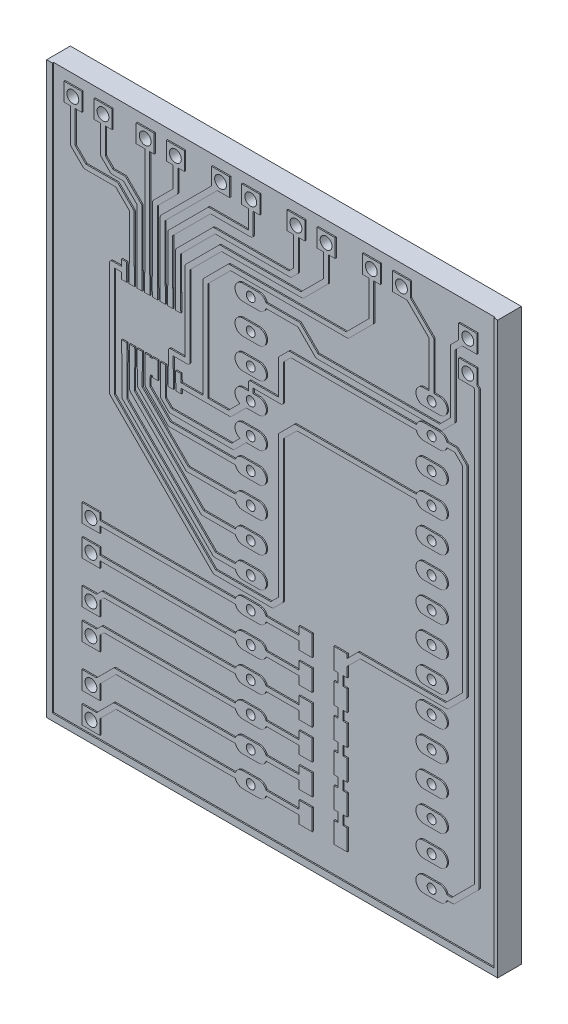
SolidWorks part; units mm, degrees
ref_plane "Front Plane" through (0, 0, 0) normal (0, 0, 1) x (1, 0, 0)
ref_plane "Top Plane" through (0, 0, 0) normal (0, 1, 0) x (1, 0, 0)
ref_plane "Right Plane" through (0, 0, 0) normal (1, 0, 0) x (0, 0, -1)
sketch "Model" plane through (0, 0, 0) normal (0, 0, 1) x (1, 0, 0)
  line L0 (2.413, 45.6438) -> (2.9718, 45.6438)
  line L1 (2.0066, 45.6438) -> (2.0066, 42.8498)
  line L2 (6.7831, 29.2576) -> (6.7754, 30.7326)
  line L3 (6.7754, 30.7326) -> (6.3254, 30.7302)
  line L4 (6.3254, 30.7302) -> (6.3331, 29.2553)
  line L5 (6.3331, 29.2553) -> (6.351, 29.2553)
  line L6 (7.4331, 29.261) -> (7.4253, 30.736)
  line L7 (7.4253, 30.736) -> (6.9753, 30.7336)
  line L8 (6.9753, 30.7336) -> (6.9831, 29.2587)
  line L9 (6.9831, 29.2587) -> (7.001, 29.2587)
  line L10 (8.0831, 29.2644) -> (8.0753, 30.7394)
  line L11 (8.0753, 30.7394) -> (7.6253, 30.737)
  line L12 (7.6253, 30.737) -> (7.633, 29.2621)
  line L13 (7.633, 29.2621) -> (7.651, 29.2622)
  line L14 (8.7331, 29.2678) -> (8.7324, 29.3986)
  line L15 (8.7253, 30.7428) -> (8.2753, 30.7404)
  line L16 (8.2753, 30.7404) -> (8.2831, 29.2655)
  line L18 (9.383, 29.2712) -> (9.3753, 30.7462)
  line L19 (9.3753, 30.7462) -> (8.9253, 30.7438)
  line L20 (8.9253, 30.7438) -> (8.9258, 30.6521)
  line L21 (8.933, 29.2689) -> (9.383, 29.2712)
  line L22 (10.033, 29.2746) -> (10.0253, 30.7496)
  line L23 (10.0253, 30.7496) -> (9.5753, 30.7473)
  line L24 (9.5753, 30.7473) -> (9.583, 29.2723)
  line L25 (9.583, 29.2723) -> (9.601, 29.2724)
  line L26 (10.683, 29.278) -> (10.6753, 30.753)
  line L27 (10.6753, 30.753) -> (10.6574, 30.7529)
  line L28 (10.2253, 30.7507) -> (10.233, 29.2757)
  line L29 (10.233, 29.2757) -> (10.683, 29.278)
  line L30 (11.333, 29.2814) -> (11.3309, 29.6926)
  line L31 (11.3253, 30.7564) -> (10.8753, 30.7541)
  line L32 (10.8753, 30.7541) -> (10.883, 29.2791)
  line L33 (10.883, 29.2791) -> (11.333, 29.2814)
  line L34 (11.3022, 35.1574) -> (11.2945, 36.6323)
  line L35 (11.2945, 36.6323) -> (11.2766, 36.6323)
  line L36 (10.8445, 36.63) -> (10.8522, 35.155)
  line L37 (10.8522, 35.155) -> (11.3022, 35.1574)
  line L38 (10.6523, 35.154) -> (10.6445, 36.6289)
  line L39 (10.6445, 36.6289) -> (10.6266, 36.6289)
  line L40 (10.1945, 36.6266) -> (10.2023, 35.1516)
  line L41 (10.2023, 35.1516) -> (10.6523, 35.154)
  line L42 (10.0023, 35.1506) -> (9.9946, 36.6255)
  line L43 (9.9946, 36.6255) -> (9.9766, 36.6254)
  line L44 (9.5445, 36.6232) -> (9.5523, 35.1482)
  line L45 (9.5523, 35.1482) -> (10.0023, 35.1506)
  line L46 (9.3523, 35.1472) -> (9.3445, 36.6221)
  line L47 (9.3445, 36.6221) -> (9.3266, 36.622)
  line L48 (8.8945, 36.6198) -> (8.9023, 35.1448)
  line L49 (8.9023, 35.1448) -> (9.3523, 35.1472)
  line L50 (8.7023, 35.1438) -> (8.6946, 36.6187)
  line L51 (8.6946, 36.6187) -> (8.6766, 36.6186)
  line L52 (8.2446, 36.6164) -> (8.2523, 35.1414)
  line L53 (8.2523, 35.1414) -> (8.7023, 35.1438)
  line L54 (8.0523, 35.1403) -> (8.0446, 36.6153)
  line L55 (8.0446, 36.6153) -> (8.0266, 36.6152)
  line L56 (7.5946, 36.613) -> (7.6023, 35.138)
  line L57 (7.6023, 35.138) -> (8.0523, 35.1403)
  line L58 (7.4023, 35.1369) -> (7.3946, 36.6119)
  line L59 (7.3946, 36.6119) -> (7.3766, 36.6118)
  line L60 (6.9446, 36.6096) -> (6.9523, 35.1346)
  line L61 (6.9523, 35.1346) -> (7.4023, 35.1369)
  line L62 (6.7523, 35.1335) -> (6.7446, 36.6085)
  line L63 (6.7446, 36.6085) -> (6.2946, 36.6062)
  line L64 (6.2946, 36.6062) -> (6.2974, 36.0731)
  line L65 (6.3023, 35.1312) -> (6.7523, 35.1335)
  line L66 (2.9718, 14.6558) -> (2.9718, 13.1318)
  line L67 (2.9718, 13.1318) -> (4.4958, 13.1318)
  line L68 (4.4958, 13.1318) -> (4.4958, 13.6906)
  line L69 (4.4958, 14.6558) -> (2.9718, 14.6558)
  line L70 (16.5354, 39.2938) -> (17.8562, 39.2938) construction
  line L71 (4.5466, 45.6438) -> (4.5466, 43.3578)
  line L72 (4.953, 45.6438) -> (5.5118, 45.6438)
  line L73 (16.5354, 39.9573) -> (17.8562, 39.9573)
  line L74 (2.9718, 17.1958) -> (2.9718, 15.6718)
  line L75 (2.9718, 15.6718) -> (4.4958, 15.6718)
  line L76 (4.4958, 15.6718) -> (4.4958, 16.2306)
  line L77 (4.4958, 17.1958) -> (2.9718, 17.1958)
  line L78 (8.2702, 45.6438) -> (8.2702, 36.6165)
  line L79 (8.6766, 45.6438) -> (9.0678, 45.6438)
  line L80 (16.5354, 38.6303) -> (17.8562, 38.6303)
  line L81 (10.6426, 45.6438) -> (10.6426, 43.8944)
  line L82 (2.9718, 8.5598) -> (2.9718, 7.0358)
  line L83 (2.9718, 7.0358) -> (4.4958, 7.0358)
  line L84 (4.4958, 7.0358) -> (4.4958, 8.2724)
  line L85 (4.2084, 8.5598) -> (2.9718, 8.5598)
  line L86 (11.049, 45.6438) -> (11.6078, 45.6438)
  line L87 (17.1958, 39.2938) -> (17.1958, 36.7538) construction
  line L88 (13.8938, 45.7336) -> (9.6297, 41.4695)
  line L89 (31.7754, 39.2938) -> (33.0962, 39.2938) construction
  line L90 (2.9718, 11.0998) -> (2.9718, 9.5758)
  line L91 (2.9718, 9.5758) -> (4.4958, 9.5758)
  line L92 (4.4958, 9.5758) -> (4.4958, 10.8124)
  line L93 (4.2084, 11.0998) -> (2.9718, 11.0998)
  line L94 (17.399, 45.6438) -> (17.9578, 45.6438)
  line L95 (20.8026, 45.6438) -> (20.8026, 43.188)
  line L96 (21.209, 45.6438) -> (21.7678, 45.6438)
  line L97 (18.4879, 39.0906) -> (21.1756, 39.0906)
  line L98 (2.9718, 2.4638) -> (2.9718, 0.9398)
  line L99 (2.9718, 0.9398) -> (4.4958, 0.9398)
  line L100 (4.4958, 0.9398) -> (4.4958, 2.1764)
  line L101 (4.2084, 2.4638) -> (2.9718, 2.4638)
  line L102 (23.3426, 45.6438) -> (23.3426, 43.696)
  line L103 (23.749, 45.6438) -> (24.3078, 45.6438)
  line L104 (31.7754, 39.9573) -> (33.0962, 39.9573)
  line L105 (27.1526, 45.6438) -> (27.1526, 42.68)
  line L106 (2.9718, 5.0038) -> (2.9718, 3.4798)
  line L107 (2.9718, 3.4798) -> (4.4958, 3.4798)
  line L108 (4.4958, 3.4798) -> (4.4958, 4.7164)
  line L109 (4.2084, 5.0038) -> (2.9718, 5.0038)
  line L110 (27.559, 45.6438) -> (28.1178, 45.6438)
  line L111 (31.7754, 38.6303) -> (33.0962, 38.6303)
  line L112 (31.7754, 36.7538) -> (33.0962, 36.7538) construction
  line L113 (30.3704, 45.6438) -> (32.2326, 43.7816)
  line L114 (3.9878, 45.6438) -> (4.5466, 45.6438)
  line L115 (5.5118, 45.6438) -> (5.5118, 47.1678)
  line L116 (5.5118, 47.1678) -> (3.9878, 47.1678)
  line L117 (3.9878, 47.1678) -> (3.9878, 45.6438)
  line L118 (34.7218, 44.9152) -> (34.0701, 44.2635)
  line L119 (31.7754, 37.4173) -> (33.0962, 37.4173)
  line L120 (31.7754, 36.0903) -> (33.0962, 36.0903)
  line L121 (4.4958, 2.1764) -> (5.85, 3.5306)
  line L122 (1.4478, 45.6438) -> (2.0066, 45.6438)
  line L123 (2.9718, 45.6438) -> (2.9718, 47.1678)
  line L124 (2.9718, 47.1678) -> (1.4478, 47.1678)
  line L125 (1.4478, 47.1678) -> (1.4478, 45.6438)
  line L126 (31.7754, 34.2138) -> (33.0962, 34.2138) construction
  line L127 (4.4958, 4.7164) -> (5.85, 6.0706)
  line L128 (31.7754, 34.8773) -> (33.0962, 34.8773)
  line L129 (4.4958, 8.2724) -> (4.834, 8.6106)
  line L130 (10.0838, 45.6438) -> (10.6426, 45.6438)
  line L131 (11.6078, 45.6438) -> (11.6078, 47.1678)
  line L132 (11.6078, 47.1678) -> (10.0838, 47.1678)
  line L133 (10.0838, 47.1678) -> (10.0838, 45.6438)
  line L134 (31.7754, 33.5503) -> (33.0962, 33.5503)
  line L135 (4.4958, 10.8124) -> (4.834, 11.1506)
  line L136 (31.7754, 31.6738) -> (33.0962, 31.6738) construction
  line L137 (4.4958, 13.6906) -> (7.2898, 13.6906)
  line L138 (7.5438, 45.6438) -> (8.2702, 45.6438)
  line L139 (9.0678, 45.6438) -> (9.0678, 47.1678)
  line L140 (9.0678, 47.1678) -> (7.5438, 47.1678)
  line L141 (7.5438, 47.1678) -> (7.5438, 45.6438)
  line L142 (4.4958, 14.097) -> (4.4958, 14.6558)
  line L143 (31.7754, 32.3373) -> (33.0962, 32.3373)
  line L144 (4.4958, 16.2306) -> (7.2898, 16.2306)
  line L145 (4.4958, 16.637) -> (4.4958, 17.1958)
  line L146 (16.4338, 45.6438) -> (16.9926, 45.6438)
  line L147 (17.9578, 45.6438) -> (17.9578, 47.1678)
  line L148 (17.9578, 47.1678) -> (16.4338, 47.1678)
  line L149 (16.4338, 47.1678) -> (16.4338, 45.6438)
  line L150 (31.7754, 31.0103) -> (33.0962, 31.0103)
  line L151 (6.9702, 36.6097) -> (6.9446, 36.6096)
  line L152 (7.6202, 36.6131) -> (7.5946, 36.613)
  line L153 (8.2702, 36.6165) -> (8.2446, 36.6164)
  line L154 (14.3788, 45.6438) -> (15.4178, 45.6438)
  line L155 (15.4178, 45.6438) -> (15.4178, 47.1678)
  line L156 (15.4178, 47.1678) -> (13.8938, 47.1678)
  line L157 (13.8938, 47.1678) -> (13.8938, 45.7336)
  line L158 (8.9202, 36.6199) -> (8.8945, 36.6198)
  line L159 (9.5702, 36.6233) -> (9.5445, 36.6232)
  line L160 (10.2202, 36.6267) -> (10.1945, 36.6266)
  line L161 (10.8702, 36.6301) -> (10.8445, 36.63)
  line L162 (29.1338, 45.6438) -> (30.3704, 45.6438)
  line L163 (30.6578, 45.9312) -> (30.6578, 47.1678)
  line L164 (30.6578, 47.1678) -> (29.1338, 47.1678)
  line L165 (29.1338, 47.1678) -> (29.1338, 45.6438)
  line L166 (6.7574, 29.2575) -> (6.7831, 29.2576)
  line L167 (7.4074, 29.2609) -> (7.4331, 29.261)
  line L168 (8.0574, 29.2643) -> (8.0831, 29.2644)
  line L170 (26.5938, 45.6438) -> (27.1526, 45.6438)
  line L171 (28.1178, 45.6438) -> (28.1178, 47.1678)
  line L172 (28.1178, 47.1678) -> (26.5938, 47.1678)
  line L173 (26.5938, 47.1678) -> (26.5938, 45.6438)
  line L174 (10.0074, 29.2745) -> (10.033, 29.2746)
  line L175 (10.251, 30.7508) -> (10.2253, 30.7507)
  line L176 (11.3287, 30.099) -> (11.3253, 30.7564)
  line L177 (24.9682, 15.5575) -> (25.3238, 15.5575)
  line L178 (22.7838, 45.6438) -> (23.3426, 45.6438)
  line L179 (24.3078, 45.6438) -> (24.3078, 47.1678)
  line L180 (24.3078, 47.1678) -> (22.7838, 47.1678)
  line L181 (22.7838, 47.1678) -> (22.7838, 45.6438)
  line L182 (24.5618, 14.7701) -> (24.2062, 14.7701)
  line L183 (24.9682, 13.0175) -> (25.3238, 13.0175)
  line L184 (24.5618, 12.2301) -> (24.2062, 12.2301)
  line L185 (24.9682, 10.4775) -> (25.3238, 10.4775)
  line L186 (20.2438, 45.6438) -> (20.8026, 45.6438)
  line L187 (21.7678, 45.6438) -> (21.7678, 47.1678)
  line L188 (21.7678, 47.1678) -> (20.2438, 47.1678)
  line L189 (20.2438, 47.1678) -> (20.2438, 45.6438)
  line L190 (24.5618, 9.6901) -> (24.2062, 9.6901)
  line L191 (24.9682, 7.9375) -> (25.3238, 7.9375)
  line L192 (24.5618, 7.1501) -> (24.2062, 7.1501)
  line L193 (24.9682, 5.3975) -> (25.3238, 5.3975)
  line L194 (34.7218, 43.6118) -> (34.7218, 42.0878)
  line L195 (34.7218, 42.0878) -> (35.9584, 42.0878)
  line L196 (36.2458, 42.3752) -> (36.2458, 43.6118)
  line L197 (36.2458, 43.6118) -> (34.7218, 43.6118)
  line L198 (24.5618, 4.6101) -> (24.2062, 4.6101)
  line L199 (8.9324, 29.3986) -> (8.933, 29.2689)
  line L200 (8.7258, 30.6521) -> (8.7253, 30.7428)
  line L201 (21.2598, 11.1506) -> (21.2598, 10.4775)
  line L202 (34.7218, 46.1518) -> (34.7218, 44.9152)
  line L203 (35.0092, 44.6278) -> (36.2458, 44.6278)
  line L204 (36.2458, 44.6278) -> (36.2458, 46.1518)
  line L205 (36.2458, 46.1518) -> (34.7218, 46.1518)
  line L206 (21.2598, 13.6906) -> (21.2598, 13.0175)
  line L207 (21.2598, 16.2306) -> (21.2598, 15.5575)
  line L208 (21.2598, 3.5306) -> (21.2598, 2.8575)
  line L209 (21.2598, 6.0706) -> (21.2598, 5.3975)
  line L210 (21.2598, 15.5575) -> (22.3774, 15.5575)
  line L211 (22.3774, 15.5575) -> (22.3774, 17.3101)
  line L212 (22.3774, 17.3101) -> (21.2598, 17.3101)
  line L213 (21.2598, 17.3101) -> (21.2598, 16.637)
  line L214 (24.2062, 15.5575) -> (24.5618, 15.5575)
  line L215 (25.3238, 15.5575) -> (25.3238, 16.4004)
  line L216 (25.3238, 17.3101) -> (24.2062, 17.3101)
  line L217 (24.2062, 17.3101) -> (24.2062, 15.5575)
  line L218 (21.2598, 13.0175) -> (22.3774, 13.0175)
  line L219 (22.3774, 13.0175) -> (22.3774, 14.7701)
  line L220 (22.3774, 14.7701) -> (21.2598, 14.7701)
  line L221 (21.2598, 14.7701) -> (21.2598, 14.097)
  line L222 (24.2062, 13.0175) -> (24.5618, 13.0175)
  line L223 (25.3238, 13.0175) -> (25.3238, 14.7701)
  line L224 (25.3238, 14.7701) -> (24.9682, 14.7701)
  line L225 (24.2062, 14.7701) -> (24.2062, 13.0175)
  line L226 (21.2598, 10.4775) -> (22.3774, 10.4775)
  line L227 (22.3774, 10.4775) -> (22.3774, 12.2301)
  line L228 (22.3774, 12.2301) -> (21.2598, 12.2301)
  line L229 (21.2598, 12.2301) -> (21.2598, 11.557)
  line L230 (24.2062, 10.4775) -> (24.5618, 10.4775)
  line L231 (25.3238, 10.4775) -> (25.3238, 12.2301)
  line L232 (25.3238, 12.2301) -> (24.9682, 12.2301)
  line L233 (24.2062, 12.2301) -> (24.2062, 10.4775)
  line L234 (21.2598, 7.9375) -> (22.3774, 7.9375)
  line L235 (22.3774, 7.9375) -> (22.3774, 9.6901)
  line L236 (22.3774, 9.6901) -> (21.2598, 9.6901)
  line L237 (21.2598, 9.6901) -> (21.2598, 9.017)
  line L238 (24.2062, 7.9375) -> (24.5618, 7.9375)
  line L239 (25.3238, 7.9375) -> (25.3238, 9.6901)
  line L240 (25.3238, 9.6901) -> (24.9682, 9.6901)
  line L241 (24.2062, 9.6901) -> (24.2062, 7.9375)
  line L242 (21.2598, 5.3975) -> (22.3774, 5.3975)
  line L243 (22.3774, 5.3975) -> (22.3774, 7.1501)
  line L244 (22.3774, 7.1501) -> (21.2598, 7.1501)
  line L245 (21.2598, 7.1501) -> (21.2598, 6.477)
  line L246 (24.2062, 5.3975) -> (24.5618, 5.3975)
  line L247 (25.3238, 5.3975) -> (25.3238, 7.1501)
  line L248 (25.3238, 7.1501) -> (24.9682, 7.1501)
  line L249 (24.2062, 7.1501) -> (24.2062, 5.3975)
  line L250 (21.2598, 2.8575) -> (22.3774, 2.8575)
  line L251 (22.3774, 2.8575) -> (22.3774, 4.6101)
  line L252 (22.3774, 4.6101) -> (21.2598, 4.6101)
  line L253 (21.2598, 4.6101) -> (21.2598, 3.937)
  line L254 (24.2062, 2.8575) -> (25.3238, 2.8575)
  line L255 (25.3238, 2.8575) -> (25.3238, 4.6101)
  line L256 (25.3238, 4.6101) -> (24.9682, 4.6101)
  line L257 (24.2062, 4.6101) -> (24.2062, 2.8575)
  line L258 (31.7754, 29.1338) -> (33.0962, 29.1338) construction
  line L259 (31.7754, 29.7973) -> (33.0962, 29.7973)
  line L260 (31.7754, 28.4703) -> (33.0962, 28.4703)
  line L261 (31.7754, 26.5938) -> (33.0962, 26.5938) construction
  line L262 (31.7754, 27.2573) -> (33.0962, 27.2573)
  line L263 (31.7754, 25.9303) -> (33.0962, 25.9303)
  line L264 (31.7754, 24.0538) -> (33.0962, 24.0538) construction
  line L265 (31.7754, 24.7173) -> (33.0962, 24.7173)
  line L266 (31.7754, 23.3903) -> (33.0962, 23.3903)
  line L267 (31.7754, 21.5138) -> (33.0962, 21.5138) construction
  line L268 (31.7754, 22.1773) -> (33.0962, 22.1773)
  line L269 (31.7754, 20.8503) -> (33.0962, 20.8503)
  line L270 (31.7754, 18.9738) -> (33.0962, 18.9738) construction
  line L271 (31.7754, 19.6373) -> (33.0962, 19.6373)
  line L272 (31.7754, 18.3103) -> (33.0962, 18.3103)
  line L273 (31.7754, 16.4338) -> (33.0962, 16.4338) construction
  line L274 (31.7754, 17.0973) -> (33.0962, 17.0973)
  line L275 (31.7754, 15.7703) -> (33.0962, 15.7703)
  line L276 (31.7754, 13.8938) -> (33.0962, 13.8938) construction
  line L277 (31.7754, 14.5573) -> (33.0962, 14.5573)
  line L278 (31.7754, 13.2303) -> (33.0962, 13.2303)
  line L279 (31.7754, 11.3538) -> (33.0962, 11.3538) construction
  line L280 (31.7754, 12.0173) -> (33.0962, 12.0173)
  line L281 (31.7754, 10.6903) -> (33.0962, 10.6903)
  line L282 (31.7754, 8.8138) -> (33.0962, 8.8138) construction
  line L283 (31.7754, 9.4773) -> (33.0962, 9.4773)
  line L284 (31.7754, 8.1503) -> (33.0962, 8.1503)
  line L285 (31.7754, 6.2738) -> (33.0962, 6.2738) construction
  line L286 (31.7754, 6.9373) -> (33.0962, 6.9373)
  line L287 (31.7754, 5.6103) -> (33.0962, 5.6103)
  line L288 (31.7754, 3.7338) -> (33.0962, 3.7338) construction
  line L289 (31.7754, 4.3973) -> (33.0962, 4.3973)
  line L290 (31.7754, 3.0703) -> (33.0962, 3.0703)
  line L291 (16.5354, 36.7538) -> (17.8562, 36.7538) construction
  line L292 (16.5354, 37.4173) -> (17.8562, 37.4173)
  line L293 (16.5354, 36.0903) -> (17.8562, 36.0903)
  line L294 (16.5354, 34.2138) -> (17.8562, 34.2138) construction
  line L295 (16.5354, 34.8773) -> (17.8562, 34.8773)
  line L296 (16.5354, 33.5503) -> (17.8562, 33.5503)
  line L297 (16.5354, 31.6738) -> (17.8562, 31.6738) construction
  line L298 (16.5354, 32.3373) -> (16.9926, 32.3373)
  line L299 (16.8196, 31.0103) -> (17.8562, 31.0103)
  line L300 (16.5354, 29.1338) -> (17.8562, 29.1338) construction
  line L301 (16.5354, 29.7973) -> (17.8562, 29.7973)
  line L302 (16.8196, 28.4703) -> (17.8562, 28.4703)
  line L303 (16.5354, 26.5938) -> (17.8562, 26.5938) construction
  line L304 (16.5354, 27.2573) -> (17.8562, 27.2573)
  line L305 (16.5354, 25.9303) -> (17.8562, 25.9303)
  line L306 (16.5354, 24.0538) -> (17.8562, 24.0538) construction
  line L307 (16.5354, 24.7173) -> (17.8562, 24.7173)
  line L308 (16.5354, 23.3903) -> (17.8562, 23.3903)
  line L309 (16.5354, 21.5138) -> (17.8562, 21.5138) construction
  line L310 (16.5354, 22.1773) -> (17.8562, 22.1773)
  line L311 (16.5354, 20.8503) -> (17.8562, 20.8503)
  line L312 (16.5354, 18.9738) -> (17.8562, 18.9738) construction
  line L313 (16.5354, 19.6373) -> (17.8562, 19.6373)
  line L314 (16.5354, 18.3103) -> (17.8562, 18.3103)
  line L315 (16.5354, 16.4338) -> (17.8562, 16.4338) construction
  line L316 (16.5354, 17.0973) -> (17.8562, 17.0973)
  line L317 (16.5354, 15.7703) -> (17.8562, 15.7703)
  line L318 (16.5354, 13.8938) -> (17.8562, 13.8938) construction
  line L319 (16.5354, 14.5573) -> (17.8562, 14.5573)
  line L320 (16.5354, 13.2303) -> (17.8562, 13.2303)
  line L321 (16.5354, 11.3538) -> (17.8562, 11.3538) construction
  line L322 (16.5354, 12.0173) -> (17.8562, 12.0173)
  line L323 (16.5354, 10.6903) -> (17.8562, 10.6903)
  line L324 (16.5354, 8.8138) -> (17.8562, 8.8138) construction
  line L325 (16.5354, 9.4773) -> (17.8562, 9.4773)
  line L326 (16.5354, 8.1503) -> (17.8562, 8.1503)
  line L327 (16.5354, 6.2738) -> (17.8562, 6.2738) construction
  line L328 (16.5354, 6.9373) -> (17.8562, 6.9373)
  line L329 (16.5354, 5.6103) -> (17.8562, 5.6103)
  line L330 (16.5354, 3.7338) -> (17.8562, 3.7338) construction
  line L331 (16.5354, 4.3973) -> (17.8562, 4.3973)
  line L332 (16.5354, 3.0703) -> (17.8562, 3.0703)
  line L333 (17.399, 32.3373) -> (17.8562, 32.3373)
  line L334 (16.2914, 28.5168) -> (15.5876, 27.813)
  line L335 (17.399, 32.3373) -> (17.399, 32.7406)
  line L336 (16.2914, 31.0568) -> (15.3336, 30.099)
  line L337 (15.9037, 26.797) -> (10.422, 26.797)
  line L338 (15.9037, 24.257) -> (11.946, 24.257)
  line L339 (15.9037, 21.717) -> (13.216, 21.717)
  line L340 (15.9037, 19.177) -> (14.232, 19.177)
  line L341 (15.9037, 16.637) -> (7.2898, 16.637)
  line L342 (15.9037, 14.097) -> (7.2898, 14.097)
  line L343 (15.9037, 11.557) -> (4.7498, 11.557)
  line L344 (18.4879, 13.6906) -> (21.2598, 13.6906)
  line L345 (31.1437, 36.957) -> (20.4978, 36.957)
  line L346 (18.4879, 11.1506) -> (19.9898, 11.1506)
  line L347 (18.4879, 8.6106) -> (21.2598, 8.6106)
  line L348 (18.4879, 6.0706) -> (21.2598, 6.0706)
  line L349 (15.9037, 9.017) -> (4.7498, 9.017)
  line L350 (18.4879, 3.5306) -> (21.2598, 3.5306)
  line L351 (15.9037, 6.477) -> (5.7658, 6.477)
  line L352 (33.7279, 3.5306) -> (34.2138, 3.5306)
  line L353 (15.9037, 3.937) -> (5.7658, 3.937)
  line L354 (31.1437, 31.877) -> (21.0058, 31.877)
  line L356 (33.7279, 36.5506) -> (34.3836, 36.5506)
  line L357 (8.9258, 30.6521) -> (8.7258, 30.6521)
  line L358 (8.9324, 29.3986) -> (8.7324, 29.3986)
  line L502 (0.4976, 48.429) -> (37.6832, 48.429)
  line L504 (37.6832, 48.429) -> (37.6832, 0.5754)
  line L506 (37.6832, 0.5754) -> (0.4976, 0.5754)
  line L508 (0.4976, 0.5754) -> (0.4976, 48.429)
  line L510 (13.589, 30.099) -> (13.589, 38.4476)
  line L511 (13.1826, 38.5318) -> (13.1826, 30.099)
  line L512 (19.939, 32.9438) -> (19.939, 35.9076)
  line L513 (19.5326, 35.9918) -> (19.5326, 33.147)
  line L514 (19.5326, 33.147) -> (17.1958, 33.147)
  line L515 (17.399, 32.7406) -> (19.7358, 32.7406)
  line L516 (16.9926, 32.9438) -> (16.9926, 32.3373)
  line L519 (34.4678, 36.957) -> (33.7279, 36.957)
  line L520 (24.5618, 15.5575) -> (24.5618, 14.7701)
  line L521 (24.9682, 14.7701) -> (24.9682, 15.5575)
  line L522 (24.5618, 13.0175) -> (24.5618, 12.2301)
  line L523 (24.9682, 12.2301) -> (24.9682, 13.0175)
  line L524 (24.5618, 10.4775) -> (24.5618, 9.6901)
  line L525 (24.9682, 9.6901) -> (24.9682, 10.4775)
  line L526 (24.5618, 7.9375) -> (24.5618, 7.1501)
  line L527 (24.9682, 7.1501) -> (24.9682, 7.9375)
  line L528 (24.5618, 5.3975) -> (24.5618, 4.6101)
  line L529 (24.9682, 4.6101) -> (24.9682, 5.3975)
  line L530 (25.4675, 40.4201) -> (27.4995, 42.4521)
  line L531 (27.1526, 42.68) -> (25.2396, 40.767)
  line L532 (27.559, 42.5958) -> (27.559, 45.6438)
  line L534 (15.5615, 29.7521) -> (16.8196, 31.0103)
  line L536 (21.2598, 8.6106) -> (21.2598, 7.9375)
  line L537 (25.3238, 16.9752) -> (25.3238, 17.3101)
  line L538 (13.3858, 29.6926) -> (15.4178, 29.6926)
  line L539 (15.3336, 30.099) -> (13.589, 30.099)
  line L540 (13.589, 38.4476) -> (15.502, 40.3606)
  line L541 (15.2741, 40.7075) -> (13.2421, 38.6755)
  line L542 (15.502, 40.3606) -> (25.3238, 40.3606)
  line L543 (25.2396, 40.767) -> (15.4178, 40.767)
  line L544 (19.939, 35.9076) -> (20.582, 36.5506)
  line L545 (20.3541, 36.8975) -> (19.5921, 36.1355)
  line L546 (20.582, 36.5506) -> (31.1437, 36.5506)
  line L548 (34.3836, 36.5506) -> (35.0266, 35.9076)
  line L549 (35.3735, 36.1355) -> (34.6115, 36.8975)
  line L550 (35.0266, 35.9076) -> (35.0266, 19.312)
  line L551 (35.433, 19.2278) -> (35.433, 35.9918)
  line L552 (35.0266, 19.312) -> (33.6216, 17.907)
  line L553 (33.8495, 17.5601) -> (35.3735, 19.0841)
  line L554 (33.6216, 17.907) -> (26.3398, 17.907)
  line L555 (26.424, 17.5006) -> (33.7058, 17.5006)
  line L556 (11.3309, 29.6926) -> (13.3858, 29.6926)
  line L557 (13.1826, 30.099) -> (11.3287, 30.099)
  line L558 (26.1961, 17.8475) -> (25.3238, 16.9752)
  line L559 (25.3238, 16.4004) -> (26.424, 17.5006)
  line L563 (5.6221, 3.8775) -> (4.2084, 2.4638)
  line L564 (5.85, 3.5306) -> (15.9037, 3.5306)
  line L567 (21.2598, 3.937) -> (18.4879, 3.937)
  line L569 (7.2898, 16.2306) -> (15.9037, 16.2306)
  line L570 (7.2898, 16.637) -> (4.4958, 16.637)
  line L572 (18.4879, 16.2306) -> (21.2598, 16.2306)
  line L573 (21.2598, 16.637) -> (18.4879, 16.637)
  line L575 (4.834, 11.1506) -> (15.9037, 11.1506)
  line L576 (19.9898, 11.1506) -> (21.2598, 11.1506)
  line L577 (21.2598, 11.557) -> (19.9898, 11.557)
  line L578 (19.9898, 11.557) -> (18.4879, 11.557)
  line L580 (4.6061, 11.4975) -> (4.2084, 11.0998)
  line L583 (4.834, 8.6106) -> (15.9037, 8.6106)
  line L584 (4.6061, 8.9575) -> (4.2084, 8.5598)
  line L586 (21.2598, 9.017) -> (18.4879, 9.017)
  line L588 (21.2598, 6.477) -> (18.4879, 6.477)
  line L591 (5.85, 6.0706) -> (15.9037, 6.0706)
  line L592 (5.6221, 6.4175) -> (4.2084, 5.0038)
  line L594 (7.2898, 14.097) -> (4.4958, 14.097)
  line L597 (21.2598, 14.097) -> (18.4879, 14.097)
  line L599 (7.2898, 13.6906) -> (15.9037, 13.6906)
  line L600 (6.4105, 26.4237) -> (14.0041, 18.8301)
  line L601 (14.232, 19.177) -> (6.7574, 26.6516)
  line L602 (6.351, 29.2553) -> (6.351, 26.5674)
  line L603 (6.7574, 26.6516) -> (6.7574, 29.2575)
  line L604 (14.1478, 18.7706) -> (15.9037, 18.7706)
  line L606 (7.0605, 27.2977) -> (12.9881, 21.3701)
  line L607 (13.216, 21.717) -> (7.4074, 27.5256)
  line L608 (7.001, 29.2587) -> (7.001, 27.4414)
  line L609 (7.4074, 27.5256) -> (7.4074, 29.2609)
  line L610 (13.1318, 21.3106) -> (15.9037, 21.3106)
  line L612 (7.7105, 27.9177) -> (11.7181, 23.9101)
  line L613 (11.946, 24.257) -> (8.0574, 28.1456)
  line L614 (11.8618, 23.8506) -> (15.9037, 23.8506)
  line L616 (7.651, 29.2622) -> (7.651, 28.0614)
  line L617 (8.0574, 28.1456) -> (8.0574, 29.2643)
  line L618 (35.9584, 42.0878) -> (36.0426, 42.0036)
  line L619 (8.428, 30.0075) -> (8.428, 30.0041)
  line L620 (8.3605, 28.2837) -> (10.1941, 26.4501)
  line L621 (10.422, 26.797) -> (8.7074, 28.5115)
  line L622 (10.3378, 26.3906) -> (15.9037, 26.3906)
  line L624 (8.301, 29.0068) -> (8.301, 28.4274)
  line L625 (8.7074, 28.5115) -> (8.7074, 29.0068)
  line L628 (9.9766, 36.6254) -> (9.9766, 41.2416)
  line L629 (9.5702, 41.3258) -> (9.5702, 36.6233)
  line L630 (9.9766, 41.2416) -> (14.3788, 45.6438)
  line L634 (9.6605, 28.0893) -> (10.2836, 27.4661)
  line L635 (10.5115, 27.813) -> (10.0074, 28.3171)
  line L636 (10.4273, 27.4066) -> (15.6718, 27.4066)
  line L637 (15.5876, 27.813) -> (10.5115, 27.813)
  line L638 (15.8155, 27.4661) -> (16.8196, 28.4703)
  line L640 (9.601, 29.2724) -> (9.601, 28.2329)
  line L641 (10.0074, 28.3171) -> (10.0074, 29.2745)
  line L642 (19.5326, 30.4038) -> (19.5326, 18.55)
  line L643 (19.939, 18.4658) -> (19.939, 30.3196)
  line L644 (6.2974, 36.0731) -> (5.5118, 36.0731)
  line L645 (5.715, 35.6667) -> (6.2995, 35.6667)
  line L646 (14.232, 17.907) -> (5.715, 26.424)
  line L647 (5.3681, 26.1961) -> (14.0041, 17.5601)
  line L648 (5.715, 26.424) -> (5.715, 35.6667)
  line L649 (5.3086, 35.8699) -> (5.3086, 26.3398)
  line L650 (19.939, 30.3196) -> (21.09, 31.4706)
  line L651 (20.8621, 31.8175) -> (19.5921, 30.5475)
  line L652 (21.09, 31.4706) -> (31.1437, 31.4706)
  line L654 (19.5326, 18.55) -> (18.8896, 17.907)
  line L655 (19.1175, 17.5601) -> (19.8795, 18.3221)
  line L656 (18.8896, 17.907) -> (14.232, 17.907)
  line L657 (14.1478, 17.5006) -> (18.9738, 17.5006)
  line L658 (13.8096, 43.6626) -> (17.1958, 43.6626)
  line L659 (16.9926, 44.069) -> (13.7254, 44.069)
  line L660 (10.6266, 36.6289) -> (10.6266, 40.4796)
  line L661 (10.2202, 40.5638) -> (10.2202, 36.6267)
  line L662 (10.6266, 40.4796) -> (13.8096, 43.6626)
  line L663 (13.5817, 44.0095) -> (10.2797, 40.7075)
  line L664 (17.399, 43.8658) -> (17.399, 45.6438)
  line L665 (16.9926, 45.6438) -> (16.9926, 44.069)
  line L670 (7.3766, 36.6118) -> (7.3766, 40.5638)
  line L671 (6.9702, 40.4796) -> (6.9702, 36.6097)
  line L672 (7.3171, 40.7075) -> (6.0471, 41.9775)
  line L673 (5.8193, 41.6306) -> (6.9702, 40.4796)
  line L674 (5.9034, 42.037) -> (3.31, 42.037)
  line L675 (3.2258, 41.6306) -> (5.8193, 41.6306)
  line L676 (3.31, 42.037) -> (2.413, 42.934)
  line L677 (2.0661, 42.7061) -> (3.0821, 41.6901)
  line L678 (2.413, 42.934) -> (2.413, 45.6438)
  line L680 (6.2995, 35.6667) -> (6.3023, 35.1312)
  line L682 (8.0266, 36.6152) -> (8.0266, 41.3258)
  line L683 (7.6202, 41.2416) -> (7.6202, 36.6131)
  line L684 (7.9671, 41.4695) -> (6.6971, 42.7395)
  line L685 (6.4693, 42.3926) -> (7.6202, 41.2416)
  line L686 (6.5534, 42.799) -> (5.596, 42.799)
  line L687 (5.5118, 42.3926) -> (6.4693, 42.3926)
  line L688 (5.596, 42.799) -> (4.953, 43.442)
  line L689 (4.6061, 43.2141) -> (5.3681, 42.4521)
  line L690 (4.953, 43.442) -> (4.953, 45.6438)
  line L692 (8.6766, 36.6186) -> (8.6766, 45.6438)
  line L696 (9.3266, 36.622) -> (9.3266, 42.0036)
  line L697 (8.9202, 42.0878) -> (8.9202, 36.6199)
  line L698 (11.049, 43.8102) -> (11.049, 45.6438)
  line L700 (9.3266, 42.0036) -> (10.9895, 43.6665)
  line L701 (10.6426, 43.8944) -> (8.9797, 42.2315)
  line L702 (11.2766, 36.6323) -> (11.2766, 39.4636)
  line L703 (10.8702, 39.5478) -> (10.8702, 36.6301)
  line L704 (14.2056, 42.3926) -> (20.4978, 42.3926)
  line L705 (20.4136, 42.799) -> (14.1214, 42.799)
  line L706 (11.2766, 39.4636) -> (14.2056, 42.3926)
  line L707 (13.9777, 42.7395) -> (10.9297, 39.6915)
  line L708 (20.6415, 42.4521) -> (21.1495, 42.9601)
  line L709 (20.8026, 43.188) -> (20.4136, 42.799)
  line L710 (21.209, 43.1038) -> (21.209, 45.6438)
  line L712 (10.6574, 31.7246) -> (11.8618, 31.7246)
  line L713 (11.6586, 32.131) -> (10.4542, 32.131)
  line L714 (10.6574, 30.7529) -> (10.6574, 31.7246)
  line L715 (10.251, 31.9278) -> (10.251, 30.7508)
  line L716 (21.6575, 41.4361) -> (23.6895, 43.4681)
  line L717 (23.3426, 43.696) -> (21.4296, 41.783)
  line L718 (23.749, 43.6118) -> (23.749, 45.6438)
  line L720 (12.065, 31.9278) -> (12.065, 38.7016)
  line L721 (11.6586, 38.7858) -> (11.6586, 32.131)
  line L722 (12.065, 38.7016) -> (14.74, 41.3766)
  line L723 (14.5121, 41.7235) -> (11.7181, 38.9295)
  line L724 (14.74, 41.3766) -> (21.5138, 41.3766)
  line L725 (21.4296, 41.783) -> (14.6558, 41.783)
  line L726 (22.868, 37.973) -> (21.4035, 39.4375)
  line L727 (21.1756, 39.0906) -> (22.6401, 37.6261)
  line L729 (21.2598, 39.497) -> (18.4879, 39.497)
  line L730 (34.0106, 44.1198) -> (34.0106, 38.87)
  line L731 (34.417, 38.7858) -> (34.417, 44.0356)
  line L733 (34.417, 44.0356) -> (35.0092, 44.6278)
  line L734 (34.0106, 38.87) -> (33.1136, 37.973)
  line L735 (33.3415, 37.6261) -> (34.3575, 38.6421)
  line L736 (33.1136, 37.973) -> (22.868, 37.973)
  line L737 (22.7838, 37.5666) -> (33.1978, 37.5666)
  line L738 (36.0426, 42.0036) -> (36.0426, 5.85)
  line L739 (36.449, 5.7658) -> (36.449, 42.0878)
  line L741 (36.3895, 42.2315) -> (36.2458, 42.3752)
  line L742 (36.0426, 5.85) -> (34.1296, 3.937)
  line L743 (34.3575, 3.5901) -> (36.3895, 5.6221)
  line L744 (34.1296, 3.937) -> (33.7279, 3.937)
  line L746 (32.639, 39.2938) -> (32.639, 43.8658)
  line L747 (32.2326, 43.7816) -> (32.2326, 39.2938)
  line L748 (32.5795, 44.0095) -> (30.6578, 45.9312)
  line L750 (8.2831, 29.2655) -> (8.301, 29.0068)
  line L751 (8.7331, 29.2678) -> (8.7074, 29.0068)
  circle A2 centre (17.1958, 39.2938) radius 0.375
  circle A3 centre (17.1958, 36.7538) radius 0.375
  circle A4 centre (17.1958, 34.2138) radius 0.375
  circle A5 centre (17.1958, 31.6738) radius 0.375
  circle A6 centre (17.1958, 29.1338) radius 0.375
  circle A7 centre (17.1958, 26.5938) radius 0.375
  circle A8 centre (17.1958, 24.0538) radius 0.375
  circle A9 centre (17.1958, 21.5138) radius 0.375
  circle A10 centre (17.1958, 18.9738) radius 0.375
  circle A11 centre (17.1958, 16.4338) radius 0.375
  circle A12 centre (17.1958, 13.8938) radius 0.375
  circle A13 centre (17.1958, 11.3538) radius 0.375
  circle A14 centre (17.1958, 8.8138) radius 0.375
  circle A15 centre (17.1958, 6.2738) radius 0.375
  circle A16 centre (17.1958, 3.7338) radius 0.375
  circle A17 centre (32.4358, 3.7338) radius 0.375
  circle A18 centre (32.4358, 6.2738) radius 0.375
  circle A19 centre (32.4358, 8.8138) radius 0.375
  circle A20 centre (32.4358, 11.3538) radius 0.375
  circle A21 centre (32.4358, 13.8938) radius 0.375
  circle A22 centre (32.4358, 16.4338) radius 0.375
  circle A23 centre (32.4358, 18.9738) radius 0.375
  circle A24 centre (32.4358, 21.5138) radius 0.375
  circle A25 centre (32.4358, 24.0538) radius 0.375
  circle A26 centre (32.4358, 26.5938) radius 0.375
  circle A27 centre (32.4358, 29.1338) radius 0.375
  circle A28 centre (32.4358, 31.6738) radius 0.375
  circle A29 centre (32.4358, 34.2138) radius 0.375
  circle A30 centre (32.4358, 39.2938) radius 0.375
  circle A31 centre (32.4358, 36.7538) radius 0.375
  circle A32 centre (2.2098, 46.4058) radius 0.5
  circle A33 centre (4.7498, 46.4058) radius 0.5
  circle A34 centre (8.3058, 46.4058) radius 0.5
  circle A35 centre (10.8458, 46.4058) radius 0.5
  circle A36 centre (14.6558, 46.4058) radius 0.5
  circle A37 centre (17.1958, 46.4058) radius 0.5
  circle A38 centre (21.0058, 46.4058) radius 0.5
  circle A39 centre (23.5458, 46.4058) radius 0.5
  circle A40 centre (27.3558, 46.4058) radius 0.5
  circle A41 centre (29.8958, 46.4058) radius 0.5
  circle A42 centre (35.4838, 45.3898) radius 0.5
  circle A43 centre (35.4838, 42.8498) radius 0.5
  circle A44 centre (3.7338, 16.4338) radius 0.5
  circle A45 centre (3.7338, 13.8938) radius 0.5
  circle A46 centre (3.7338, 10.3378) radius 0.5
  circle A47 centre (3.7338, 7.7978) radius 0.5
  circle A48 centre (3.7338, 4.2418) radius 0.5
  circle A49 centre (3.7338, 1.7018) radius 0.5
  arc A52 (13.2421, 38.6755) -> (13.1826, 38.5318) centre (13.3858, 38.5318) ccw
  arc A54 (19.5921, 36.1355) -> (19.5326, 35.9918) centre (19.7358, 35.9918) ccw
  arc A55 (19.7358, 32.7406) -> (19.939, 32.9438) centre (19.7358, 32.9438) ccw
  arc A56 (17.1958, 33.147) -> (16.9926, 32.9438) centre (17.1958, 32.9438) ccw
  arc A58 (34.6115, 36.8975) -> (34.4678, 36.957) centre (34.4678, 36.7538) ccw
  arc A60 (27.4995, 42.4521) -> (27.559, 42.5958) centre (27.3558, 42.5958) ccw
  arc A61 (25.3238, 40.3606) -> (25.4675, 40.4201) centre (25.3238, 40.5638) ccw
  arc A62 (15.4178, 29.6926) -> (15.5615, 29.7521) centre (15.4178, 29.8958) ccw
  arc A63 (15.4178, 40.767) -> (15.2741, 40.7075) centre (15.4178, 40.5638) ccw
  arc A64 (20.4978, 36.957) -> (20.3541, 36.8975) centre (20.4978, 36.7538) ccw
  arc A65 (35.433, 35.9918) -> (35.3735, 36.1355) centre (35.2298, 35.9918) ccw
  arc A66 (35.3735, 19.0841) -> (35.433, 19.2278) centre (35.2298, 19.2278) ccw
  arc A67 (16.5354, 39.9573) -> (16.5354, 38.6303) centre (16.5354, 39.2938) ccw
  arc A68 (17.8562, 38.6303) -> (18.4879, 39.0906) centre (17.8562, 39.2938) ccw
  arc A69 (33.7058, 17.5006) -> (33.8495, 17.5601) centre (33.7058, 17.7038) ccw
  arc A70 (31.7754, 39.9573) -> (31.7754, 38.6303) centre (31.7754, 39.2938) ccw
  arc A71 (33.0962, 38.6303) -> (33.0962, 39.9573) centre (33.0962, 39.2938) ccw
  arc A72 (31.7754, 37.4173) -> (31.1437, 36.957) centre (31.7754, 36.7538) ccw
  arc A73 (33.0962, 36.0903) -> (33.7279, 36.5506) centre (33.0962, 36.7538) ccw
  arc A74 (31.7754, 34.8773) -> (31.7754, 33.5503) centre (31.7754, 34.2138) ccw
  arc A75 (33.0962, 33.5503) -> (33.0962, 34.8773) centre (33.0962, 34.2138) ccw
  arc A76 (31.7754, 32.3373) -> (31.1437, 31.877) centre (31.7754, 31.6738) ccw
  arc A77 (33.0962, 31.0103) -> (33.0962, 32.3373) centre (33.0962, 31.6738) ccw
  arc A78 (26.3398, 17.907) -> (26.1961, 17.8475) centre (26.3398, 17.7038) ccw
  arc A79 (31.7754, 29.7973) -> (31.7754, 28.4703) centre (31.7754, 29.1338) ccw
  arc A80 (33.0962, 28.4703) -> (33.0962, 29.7973) centre (33.0962, 29.1338) ccw
  arc A81 (5.7658, 3.937) -> (5.6221, 3.8775) centre (5.7658, 3.7338) ccw
  arc A82 (4.7498, 11.557) -> (4.6061, 11.4975) centre (4.7498, 11.3538) ccw
  arc A83 (4.7498, 9.017) -> (4.6061, 8.9575) centre (4.7498, 8.8138) ccw
  arc A84 (31.7754, 27.2573) -> (31.7754, 25.9303) centre (31.7754, 26.5938) ccw
  arc A85 (33.0962, 25.9303) -> (33.0962, 27.2573) centre (33.0962, 26.5938) ccw
  arc A86 (5.7658, 6.477) -> (5.6221, 6.4175) centre (5.7658, 6.2738) ccw
  arc A87 (14.0041, 18.8301) -> (14.1478, 18.7706) centre (14.1478, 18.9738) ccw
  arc A88 (6.351, 26.5674) -> (6.4105, 26.4237) centre (6.5542, 26.5674) ccw
  arc A89 (12.9881, 21.3701) -> (13.1318, 21.3106) centre (13.1318, 21.5138) ccw
  arc A90 (7.001, 27.4414) -> (7.0605, 27.2977) centre (7.2042, 27.4414) ccw
  arc A91 (11.7181, 23.9101) -> (11.8618, 23.8506) centre (11.8618, 24.0538) ccw
  arc A92 (7.651, 28.0614) -> (7.7105, 27.9177) centre (7.8542, 28.0614) ccw
  arc A93 (10.1941, 26.4501) -> (10.3378, 26.3906) centre (10.3378, 26.5938) ccw
  arc A94 (31.7754, 24.7173) -> (31.7754, 23.3903) centre (31.7754, 24.0538) ccw
  arc A95 (8.301, 28.4274) -> (8.3605, 28.2837) centre (8.5042, 28.4274) ccw
  arc A96 (9.6297, 41.4695) -> (9.5702, 41.3258) centre (9.7734, 41.3258) ccw
  arc A97 (33.0962, 23.3903) -> (33.0962, 24.7173) centre (33.0962, 24.0538) ccw
  arc A98 (10.2836, 27.4661) -> (10.4273, 27.4066) centre (10.4273, 27.6098) ccw
  arc A99 (9.601, 28.2329) -> (9.6605, 28.0893) centre (9.8042, 28.2329) ccw
  arc A100 (15.6718, 27.4066) -> (15.8155, 27.4661) centre (15.6718, 27.6098) ccw
  arc A101 (19.8795, 18.3221) -> (19.939, 18.4658) centre (19.7358, 18.4658) ccw
  arc A102 (19.5921, 30.5475) -> (19.5326, 30.4038) centre (19.7358, 30.4038) ccw
  arc A103 (5.5118, 36.0731) -> (5.3086, 35.8699) centre (5.5118, 35.8699) ccw
  arc A104 (5.3086, 26.3398) -> (5.3681, 26.1961) centre (5.5118, 26.3398) ccw
  arc A106 (14.0041, 17.5601) -> (14.1478, 17.5006) centre (14.1478, 17.7038) ccw
  arc A107 (21.0058, 31.877) -> (20.8621, 31.8175) centre (21.0058, 31.6738) ccw
  arc A108 (18.9738, 17.5006) -> (19.1175, 17.5601) centre (18.9738, 17.7038) ccw
  arc A109 (17.1958, 43.6626) -> (17.399, 43.8658) centre (17.1958, 43.8658) ccw
  arc A110 (13.7254, 44.069) -> (13.5817, 44.0095) centre (13.7254, 43.8658) ccw
  arc A111 (31.7754, 22.1773) -> (31.7754, 20.8503) centre (31.7754, 21.5138) ccw
  arc A112 (33.0962, 20.8503) -> (33.0962, 22.1773) centre (33.0962, 21.5138) ccw
  arc A113 (10.2797, 40.7075) -> (10.2202, 40.5638) centre (10.4234, 40.5638) ccw
  arc A115 (31.7754, 19.6373) -> (31.7754, 18.3103) centre (31.7754, 18.9738) ccw
  arc A116 (33.0962, 18.3103) -> (33.0962, 19.6373) centre (33.0962, 18.9738) ccw
  arc A117 (31.7754, 17.0973) -> (31.7754, 15.7703) centre (31.7754, 16.4338) ccw
  arc A118 (33.0962, 15.7703) -> (33.0962, 17.0973) centre (33.0962, 16.4338) ccw
  arc A119 (31.7754, 14.5573) -> (31.7754, 13.2303) centre (31.7754, 13.8938) ccw
  arc A121 (33.0962, 13.2303) -> (33.0962, 14.5573) centre (33.0962, 13.8938) ccw
  arc A122 (7.3766, 40.5638) -> (7.3171, 40.7075) centre (7.1734, 40.5638) ccw
  arc A123 (31.7754, 12.0173) -> (31.7754, 10.6903) centre (31.7754, 11.3538) ccw
  arc A125 (33.0962, 10.6903) -> (33.0962, 12.0173) centre (33.0962, 11.3538) ccw
  arc A126 (31.7754, 9.4773) -> (31.7754, 8.1503) centre (31.7754, 8.8138) ccw
  arc A127 (33.0962, 8.1503) -> (33.0962, 9.4773) centre (33.0962, 8.8138) ccw
  arc A128 (31.7754, 6.9373) -> (31.7754, 5.6103) centre (31.7754, 6.2738) ccw
  arc A129 (6.0471, 41.9775) -> (5.9034, 42.037) centre (5.9034, 41.8338) ccw
  arc A130 (3.0821, 41.6901) -> (3.2258, 41.6306) centre (3.2258, 41.8338) ccw
  arc A131 (33.0962, 5.6103) -> (33.0962, 6.9373) centre (33.0962, 6.2738) ccw
  arc A132 (31.7754, 4.3973) -> (31.7754, 3.0703) centre (31.7754, 3.7338) ccw
  arc A133 (2.0066, 42.8498) -> (2.0661, 42.7061) centre (2.2098, 42.8498) ccw
  arc A134 (33.0962, 3.0703) -> (33.7279, 3.5306) centre (33.0962, 3.7338) ccw
  arc A136 (16.5354, 37.4173) -> (16.5354, 36.0903) centre (16.5354, 36.7538) ccw
  arc A138 (8.0266, 41.3258) -> (7.9671, 41.4695) centre (7.8234, 41.3258) ccw
  arc A139 (17.8562, 36.0903) -> (17.8562, 37.4173) centre (17.8562, 36.7538) ccw
  arc A140 (16.5354, 34.8773) -> (16.5354, 33.5503) centre (16.5354, 34.2138) ccw
  arc A141 (6.6971, 42.7395) -> (6.5534, 42.799) centre (6.5534, 42.5958) ccw
  arc A142 (17.8562, 33.5503) -> (17.8562, 34.8773) centre (17.8562, 34.2138) ccw
  arc A143 (16.5354, 32.3373) -> (16.2914, 31.0568) centre (16.5354, 31.6738) ccw
  arc A145 (17.8562, 31.0103) -> (17.8562, 32.3373) centre (17.8562, 31.6738) ccw
  arc A146 (16.5354, 29.7973) -> (16.2914, 28.5168) centre (16.5354, 29.1338) ccw
  arc A147 (17.8562, 28.4703) -> (17.8562, 29.7973) centre (17.8562, 29.1338) ccw
  arc A148 (5.3681, 42.4521) -> (5.5118, 42.3926) centre (5.5118, 42.5958) ccw
  arc A149 (4.5466, 43.3578) -> (4.6061, 43.2141) centre (4.7498, 43.3578) ccw
  arc A150 (8.9797, 42.2315) -> (8.9202, 42.0878) centre (9.1234, 42.0878) ccw
  arc A153 (10.9895, 43.6665) -> (11.049, 43.8102) centre (10.8458, 43.8102) ccw
  arc A154 (10.9297, 39.6915) -> (10.8702, 39.5478) centre (11.0734, 39.5478) ccw
  arc A155 (20.4978, 42.3926) -> (20.6415, 42.4521) centre (20.4978, 42.5958) ccw
  arc A156 (14.1214, 42.799) -> (13.9777, 42.7395) centre (14.1214, 42.5958) ccw
  arc A159 (21.1495, 42.9601) -> (21.209, 43.1038) centre (21.0058, 43.1038) ccw
  arc A160 (11.8618, 31.7246) -> (12.065, 31.9278) centre (11.8618, 31.9278) ccw
  arc A161 (10.4542, 32.131) -> (10.251, 31.9278) centre (10.4542, 31.9278) ccw
  arc A163 (23.6895, 43.4681) -> (23.749, 43.6118) centre (23.5458, 43.6118) ccw
  arc A164 (21.5138, 41.3766) -> (21.6575, 41.4361) centre (21.5138, 41.5798) ccw
  arc A166 (16.5354, 27.2573) -> (15.9037, 26.797) centre (16.5354, 26.5938) ccw
  arc A167 (17.8562, 25.9303) -> (17.8562, 27.2573) centre (17.8562, 26.5938) ccw
  arc A168 (11.7181, 38.9295) -> (11.6586, 38.7858) centre (11.8618, 38.7858) ccw
  arc A169 (14.6558, 41.783) -> (14.5121, 41.7235) centre (14.6558, 41.5798) ccw
  arc A171 (21.4035, 39.4375) -> (21.2598, 39.497) centre (21.2598, 39.2938) ccw
  arc A172 (22.6401, 37.6261) -> (22.7838, 37.5666) centre (22.7838, 37.7698) ccw
  arc A173 (8.301, 30.0058) -> (8.301, 30.0041) centre (8.5042, 30.0041) ccw
  arc A176 (34.3575, 38.6421) -> (34.417, 38.7858) centre (34.2138, 38.7858) ccw
  arc A178 (34.0701, 44.2635) -> (34.0106, 44.1198) centre (34.2138, 44.1198) ccw
  arc A179 (33.1978, 37.5666) -> (33.3415, 37.6261) centre (33.1978, 37.7698) ccw
  arc A180 (16.5354, 24.7173) -> (15.9037, 24.257) centre (16.5354, 24.0538) ccw
  arc A181 (36.3895, 5.6221) -> (36.449, 5.7658) centre (36.2458, 5.7658) ccw
  arc A182 (36.449, 42.0878) -> (36.3895, 42.2315) centre (36.2458, 42.0878) ccw
  arc A183 (34.2138, 3.5306) -> (34.3575, 3.5901) centre (34.2138, 3.7338) ccw
  arc A184 (32.639, 43.8658) -> (32.5795, 44.0095) centre (32.4358, 43.8658) ccw
  arc A185 (17.8562, 23.3903) -> (17.8562, 24.7173) centre (17.8562, 24.0538) ccw
  arc A187 (16.5354, 22.1773) -> (15.9037, 21.717) centre (16.5354, 21.5138) ccw
  arc A188 (17.8562, 20.8503) -> (17.8562, 22.1773) centre (17.8562, 21.5138) ccw
  arc A190 (16.5354, 19.6373) -> (15.9037, 19.177) centre (16.5354, 18.9738) ccw
  arc A191 (17.8562, 18.3103) -> (17.8562, 19.6373) centre (17.8562, 18.9738) ccw
  arc A192 (16.5354, 17.0973) -> (15.9037, 16.637) centre (16.5354, 16.4338) ccw
  arc A194 (17.8562, 15.7703) -> (18.4879, 16.2306) centre (17.8562, 16.4338) ccw
  arc A195 (16.5354, 14.5573) -> (15.9037, 14.097) centre (16.5354, 13.8938) ccw
  arc A196 (17.8562, 13.2303) -> (18.4879, 13.6906) centre (17.8562, 13.8938) ccw
  arc A197 (16.5354, 12.0173) -> (15.9037, 11.557) centre (16.5354, 11.3538) ccw
  arc A198 (17.8562, 10.6903) -> (18.4879, 11.1506) centre (17.8562, 11.3538) ccw
  arc A199 (16.5354, 9.4773) -> (15.9037, 9.017) centre (16.5354, 8.8138) ccw
  arc A201 (17.8562, 8.1503) -> (18.4879, 8.6106) centre (17.8562, 8.8138) ccw
  arc A202 (16.5354, 6.9373) -> (15.9037, 6.477) centre (16.5354, 6.2738) ccw
  arc A203 (17.8562, 5.6103) -> (18.4879, 6.0706) centre (17.8562, 6.2738) ccw
  arc A204 (16.5354, 4.3973) -> (15.9037, 3.937) centre (16.5354, 3.7338) ccw
  arc A205 (17.8562, 3.0703) -> (18.4879, 3.5306) centre (17.8562, 3.7338) ccw
  arc A206 (18.4879, 39.497) -> (17.8562, 39.9573) centre (17.8562, 39.2938) ccw
  arc A207 (15.9037, 26.3906) -> (16.5354, 25.9303) centre (16.5354, 26.5938) ccw
  arc A208 (15.9037, 23.8506) -> (16.5354, 23.3903) centre (16.5354, 24.0538) ccw
  arc A210 (15.9037, 21.3106) -> (16.5354, 20.8503) centre (16.5354, 21.5138) ccw
  arc A211 (15.9037, 18.7706) -> (16.5354, 18.3103) centre (16.5354, 18.9738) ccw
  arc A212 (15.9037, 16.2306) -> (16.5354, 15.7703) centre (16.5354, 16.4338) ccw
  arc A213 (18.4879, 16.637) -> (17.8562, 17.0973) centre (17.8562, 16.4338) ccw
  arc A214 (15.9037, 13.6906) -> (16.5354, 13.2303) centre (16.5354, 13.8938) ccw
  arc A215 (18.4879, 14.097) -> (17.8562, 14.5573) centre (17.8562, 13.8938) ccw
  arc A216 (15.9037, 11.1506) -> (16.5354, 10.6903) centre (16.5354, 11.3538) ccw
  arc A217 (18.4879, 11.557) -> (17.8562, 12.0173) centre (17.8562, 11.3538) ccw
  arc A218 (18.4879, 9.017) -> (17.8562, 9.4773) centre (17.8562, 8.8138) ccw
  arc A220 (15.9037, 8.6106) -> (16.5354, 8.1503) centre (16.5354, 8.8138) ccw
  arc A221 (15.9037, 6.0706) -> (16.5354, 5.6103) centre (16.5354, 6.2738) ccw
  arc A222 (18.4879, 6.477) -> (17.8562, 6.9373) centre (17.8562, 6.2738) ccw
  arc A223 (18.4879, 3.937) -> (17.8562, 4.3973) centre (17.8562, 3.7338) ccw
  arc A224 (15.9037, 3.5306) -> (16.5354, 3.0703) centre (16.5354, 3.7338) ccw
  arc A225 (33.7279, 3.937) -> (33.0962, 4.3973) centre (33.0962, 3.7338) ccw
  arc A226 (31.1437, 36.5506) -> (31.7754, 36.0903) centre (31.7754, 36.7538) ccw
  arc A227 (33.7279, 36.957) -> (33.0962, 37.4173) centre (33.0962, 36.7538) ccw
  arc A228 (31.1437, 31.4706) -> (31.7754, 31.0103) centre (31.7754, 31.6738) ccw
  arc A295 (32.2326, 39.2938) -> (32.639, 39.2938) centre (32.4358, 39.2938) ccw
  point P161 (17.1958, 39.2938)
  point P237 (32.4358, 39.2938)
  point P259 (32.4358, 36.7538)
  point P281 (32.4358, 34.2138)
  point P292 (32.4358, 31.6738)
  point P307 (32.4358, 29.1338)
  point P343 (32.4358, 26.5938)
  point P379 (32.4358, 24.0538)
  point P392 (32.4358, 21.5138)
  point P412 (32.4358, 18.9738)
  point P425 (32.4358, 16.4338)
  point P439 (32.4358, 13.8938)
  point P465 (32.4358, 11.3538)
  point P480 (32.4358, 8.8138)
  point P505 (32.4358, 6.2738)
  point P514 (32.4358, 3.7338)
  point P539 (17.1958, 36.7538)
  point P546 (17.1958, 34.2138)
  point P555 (17.1958, 31.6738)
  point P568 (17.1958, 29.1338)
  point P583 (17.1958, 26.5938)
  point P597 (17.1958, 24.0538)
  point P608 (17.1958, 21.5138)
  point P626 (17.1958, 18.9738)
  point P641 (17.1958, 16.4338)
  point P653 (17.1958, 13.8938)
  point P667 (17.1958, 11.3538)
  point P756 (17.1958, 8.8138)
  point P864 (17.1958, 6.2738)
  point P871 (17.1958, 3.7338)
  point P1108 (8.8138, 32.9438)
  point P1109 (3.7338, 16.4338)
  point P1110 (3.7338, 10.3378)
  point P1111 (3.7338, 4.2418)
  point P1112 (2.2098, 46.4058)
  point P1113 (8.3058, 46.4058)
  point P1114 (14.6558, 46.4058)
  point P1115 (27.3558, 46.4058)
  point P1116 (21.0058, 46.4058)
  point P1117 (35.4838, 45.3898)
  point P1118 (23.2918, 16.4338)
  point P1119 (23.2918, 13.8938)
  point P1120 (23.2918, 11.3538)
  point P1121 (23.2918, 8.8138)
  point P1122 (23.2918, 6.2738)
  point P1123 (23.2918, 3.7338)
  point P1124 (32.4358, 21.5138)
  point P1125 (17.1958, 21.5138)
  line B0 (31.7754, 38.6334) -> (33.0962, 38.6334)
  line B1 (33.0962, 39.9542) -> (31.7754, 39.9542)
  arc B2 (33.0962, 38.6334) -> (33.0962, 39.9542) centre (33.0962, 39.2938) ccw
  arc B3 (31.7754, 39.9542) -> (31.7754, 38.6334) centre (31.7754, 39.2938) ccw
  line B4 (31.7754, 38.6334) -> (33.0962, 38.6334)
  line B5 (33.0962, 39.9542) -> (31.7754, 39.9542)
  arc B6 (33.0962, 38.6334) -> (33.0962, 39.9542) centre (33.0962, 39.2938) ccw
  arc B7 (31.7754, 39.9542) -> (31.7754, 38.6334) centre (31.7754, 39.2938) ccw
  line B8 (31.7754, 36.0934) -> (33.0962, 36.0934)
  line B9 (33.0962, 37.4142) -> (31.7754, 37.4142)
  arc B10 (33.0962, 36.0934) -> (33.0962, 37.4142) centre (33.0962, 36.7538) ccw
  arc B11 (31.7754, 37.4142) -> (31.7754, 36.0934) centre (31.7754, 36.7538) ccw
  line B12 (31.7754, 36.0934) -> (33.0962, 36.0934)
  line B13 (33.0962, 37.4142) -> (31.7754, 37.4142)
  arc B14 (33.0962, 36.0934) -> (33.0962, 37.4142) centre (33.0962, 36.7538) ccw
  arc B15 (31.7754, 37.4142) -> (31.7754, 36.0934) centre (31.7754, 36.7538) ccw
  line B16 (31.7754, 33.5534) -> (33.0962, 33.5534)
  line B17 (33.0962, 34.8742) -> (31.7754, 34.8742)
  arc B18 (33.0962, 33.5534) -> (33.0962, 34.8742) centre (33.0962, 34.2138) ccw
  arc B19 (31.7754, 34.8742) -> (31.7754, 33.5534) centre (31.7754, 34.2138) ccw
  line B20 (31.7754, 33.5534) -> (33.0962, 33.5534)
  line B21 (33.0962, 34.8742) -> (31.7754, 34.8742)
  arc B22 (33.0962, 33.5534) -> (33.0962, 34.8742) centre (33.0962, 34.2138) ccw
  arc B23 (31.7754, 34.8742) -> (31.7754, 33.5534) centre (31.7754, 34.2138) ccw
  line B24 (31.7754, 31.0134) -> (33.0962, 31.0134)
  line B25 (33.0962, 32.3342) -> (31.7754, 32.3342)
  arc B26 (33.0962, 31.0134) -> (33.0962, 32.3342) centre (33.0962, 31.6738) ccw
  arc B27 (31.7754, 32.3342) -> (31.7754, 31.0134) centre (31.7754, 31.6738) ccw
  line B28 (31.7754, 31.0134) -> (33.0962, 31.0134)
  line B29 (33.0962, 32.3342) -> (31.7754, 32.3342)
  arc B30 (33.0962, 31.0134) -> (33.0962, 32.3342) centre (33.0962, 31.6738) ccw
  arc B31 (31.7754, 32.3342) -> (31.7754, 31.0134) centre (31.7754, 31.6738) ccw
  line B32 (31.7754, 28.4734) -> (33.0962, 28.4734)
  line B33 (33.0962, 29.7942) -> (31.7754, 29.7942)
  arc B34 (33.0962, 28.4734) -> (33.0962, 29.7942) centre (33.0962, 29.1338) ccw
  arc B35 (31.7754, 29.7942) -> (31.7754, 28.4734) centre (31.7754, 29.1338) ccw
  line B36 (31.7754, 28.4734) -> (33.0962, 28.4734)
  line B37 (33.0962, 29.7942) -> (31.7754, 29.7942)
  arc B38 (33.0962, 28.4734) -> (33.0962, 29.7942) centre (33.0962, 29.1338) ccw
  arc B39 (31.7754, 29.7942) -> (31.7754, 28.4734) centre (31.7754, 29.1338) ccw
  line B40 (31.7754, 25.9334) -> (33.0962, 25.9334)
  line B41 (33.0962, 27.2542) -> (31.7754, 27.2542)
  arc B42 (33.0962, 25.9334) -> (33.0962, 27.2542) centre (33.0962, 26.5938) ccw
  arc B43 (31.7754, 27.2542) -> (31.7754, 25.9334) centre (31.7754, 26.5938) ccw
  line B44 (31.7754, 25.9334) -> (33.0962, 25.9334)
  line B45 (33.0962, 27.2542) -> (31.7754, 27.2542)
  arc B46 (33.0962, 25.9334) -> (33.0962, 27.2542) centre (33.0962, 26.5938) ccw
  arc B47 (31.7754, 27.2542) -> (31.7754, 25.9334) centre (31.7754, 26.5938) ccw
  line B48 (31.7754, 23.3934) -> (33.0962, 23.3934)
  line B49 (33.0962, 24.7142) -> (31.7754, 24.7142)
  arc B50 (33.0962, 23.3934) -> (33.0962, 24.7142) centre (33.0962, 24.0538) ccw
  arc B51 (31.7754, 24.7142) -> (31.7754, 23.3934) centre (31.7754, 24.0538) ccw
  line B52 (31.7754, 23.3934) -> (33.0962, 23.3934)
  line B53 (33.0962, 24.7142) -> (31.7754, 24.7142)
  arc B54 (33.0962, 23.3934) -> (33.0962, 24.7142) centre (33.0962, 24.0538) ccw
  arc B55 (31.7754, 24.7142) -> (31.7754, 23.3934) centre (31.7754, 24.0538) ccw
  line B56 (31.7754, 20.8534) -> (33.0962, 20.8534)
  line B57 (33.0962, 22.1742) -> (31.7754, 22.1742)
  arc B58 (33.0962, 20.8534) -> (33.0962, 22.1742) centre (33.0962, 21.5138) ccw
  arc B59 (31.7754, 22.1742) -> (31.7754, 20.8534) centre (31.7754, 21.5138) ccw
  line B60 (31.7754, 20.8534) -> (33.0962, 20.8534)
  line B61 (33.0962, 22.1742) -> (31.7754, 22.1742)
  arc B62 (33.0962, 20.8534) -> (33.0962, 22.1742) centre (33.0962, 21.5138) ccw
  arc B63 (31.7754, 22.1742) -> (31.7754, 20.8534) centre (31.7754, 21.5138) ccw
  line B64 (31.7754, 18.3134) -> (33.0962, 18.3134)
  line B65 (33.0962, 19.6342) -> (31.7754, 19.6342)
  arc B66 (33.0962, 18.3134) -> (33.0962, 19.6342) centre (33.0962, 18.9738) ccw
  arc B67 (31.7754, 19.6342) -> (31.7754, 18.3134) centre (31.7754, 18.9738) ccw
  line B68 (31.7754, 18.3134) -> (33.0962, 18.3134)
  line B69 (33.0962, 19.6342) -> (31.7754, 19.6342)
  arc B70 (33.0962, 18.3134) -> (33.0962, 19.6342) centre (33.0962, 18.9738) ccw
  arc B71 (31.7754, 19.6342) -> (31.7754, 18.3134) centre (31.7754, 18.9738) ccw
  line B72 (31.7754, 15.7734) -> (33.0962, 15.7734)
  line B73 (33.0962, 17.0942) -> (31.7754, 17.0942)
  arc B74 (33.0962, 15.7734) -> (33.0962, 17.0942) centre (33.0962, 16.4338) ccw
  arc B75 (31.7754, 17.0942) -> (31.7754, 15.7734) centre (31.7754, 16.4338) ccw
  line B76 (31.7754, 15.7734) -> (33.0962, 15.7734)
  line B77 (33.0962, 17.0942) -> (31.7754, 17.0942)
  arc B78 (33.0962, 15.7734) -> (33.0962, 17.0942) centre (33.0962, 16.4338) ccw
  arc B79 (31.7754, 17.0942) -> (31.7754, 15.7734) centre (31.7754, 16.4338) ccw
  line B80 (31.7754, 13.2334) -> (33.0962, 13.2334)
  line B81 (33.0962, 14.5542) -> (31.7754, 14.5542)
  arc B82 (33.0962, 13.2334) -> (33.0962, 14.5542) centre (33.0962, 13.8938) ccw
  arc B83 (31.7754, 14.5542) -> (31.7754, 13.2334) centre (31.7754, 13.8938) ccw
  line B84 (31.7754, 13.2334) -> (33.0962, 13.2334)
  line B85 (33.0962, 14.5542) -> (31.7754, 14.5542)
  arc B86 (33.0962, 13.2334) -> (33.0962, 14.5542) centre (33.0962, 13.8938) ccw
  arc B87 (31.7754, 14.5542) -> (31.7754, 13.2334) centre (31.7754, 13.8938) ccw
  line B88 (31.7754, 10.6934) -> (33.0962, 10.6934)
  line B89 (33.0962, 12.0142) -> (31.7754, 12.0142)
  arc B90 (33.0962, 10.6934) -> (33.0962, 12.0142) centre (33.0962, 11.3538) ccw
  arc B91 (31.7754, 12.0142) -> (31.7754, 10.6934) centre (31.7754, 11.3538) ccw
  line B92 (31.7754, 10.6934) -> (33.0962, 10.6934)
  line B93 (33.0962, 12.0142) -> (31.7754, 12.0142)
  arc B94 (33.0962, 10.6934) -> (33.0962, 12.0142) centre (33.0962, 11.3538) ccw
  arc B95 (31.7754, 12.0142) -> (31.7754, 10.6934) centre (31.7754, 11.3538) ccw
  line B96 (31.7754, 8.1534) -> (33.0962, 8.1534)
  line B97 (33.0962, 9.4742) -> (31.7754, 9.4742)
  arc B98 (33.0962, 8.1534) -> (33.0962, 9.4742) centre (33.0962, 8.8138) ccw
  arc B99 (31.7754, 9.4742) -> (31.7754, 8.1534) centre (31.7754, 8.8138) ccw
  line B100 (31.7754, 8.1534) -> (33.0962, 8.1534)
  line B101 (33.0962, 9.4742) -> (31.7754, 9.4742)
  arc B102 (33.0962, 8.1534) -> (33.0962, 9.4742) centre (33.0962, 8.8138) ccw
  arc B103 (31.7754, 9.4742) -> (31.7754, 8.1534) centre (31.7754, 8.8138) ccw
  line B104 (31.7754, 5.6134) -> (33.0962, 5.6134)
  line B105 (33.0962, 6.9342) -> (31.7754, 6.9342)
  arc B106 (33.0962, 5.6134) -> (33.0962, 6.9342) centre (33.0962, 6.2738) ccw
  arc B107 (31.7754, 6.9342) -> (31.7754, 5.6134) centre (31.7754, 6.2738) ccw
  line B108 (31.7754, 5.6134) -> (33.0962, 5.6134)
  line B109 (33.0962, 6.9342) -> (31.7754, 6.9342)
  arc B110 (33.0962, 5.6134) -> (33.0962, 6.9342) centre (33.0962, 6.2738) ccw
  arc B111 (31.7754, 6.9342) -> (31.7754, 5.6134) centre (31.7754, 6.2738) ccw
  line B112 (31.7754, 3.0734) -> (33.0962, 3.0734)
  line B113 (33.0962, 4.3942) -> (31.7754, 4.3942)
  arc B114 (33.0962, 3.0734) -> (33.0962, 4.3942) centre (33.0962, 3.7338) ccw
  arc B115 (31.7754, 4.3942) -> (31.7754, 3.0734) centre (31.7754, 3.7338) ccw
  line B116 (31.7754, 3.0734) -> (33.0962, 3.0734)
  line B117 (33.0962, 4.3942) -> (31.7754, 4.3942)
  arc B118 (33.0962, 3.0734) -> (33.0962, 4.3942) centre (33.0962, 3.7338) ccw
  arc B119 (31.7754, 4.3942) -> (31.7754, 3.0734) centre (31.7754, 3.7338) ccw
  line B120 (16.5354, 38.6334) -> (17.8562, 38.6334)
  line B121 (17.8562, 39.9542) -> (16.5354, 39.9542)
  arc B122 (17.8562, 38.6334) -> (17.8562, 39.9542) centre (17.8562, 39.2938) ccw
  arc B123 (16.5354, 39.9542) -> (16.5354, 38.6334) centre (16.5354, 39.2938) ccw
  line B124 (16.5354, 38.6334) -> (17.8562, 38.6334)
  line B125 (17.8562, 39.9542) -> (16.5354, 39.9542)
  arc B126 (17.8562, 38.6334) -> (17.8562, 39.9542) centre (17.8562, 39.2938) ccw
  arc B127 (16.5354, 39.9542) -> (16.5354, 38.6334) centre (16.5354, 39.2938) ccw
  line B128 (16.5354, 36.0934) -> (17.8562, 36.0934)
  line B129 (17.8562, 37.4142) -> (16.5354, 37.4142)
  arc B130 (17.8562, 36.0934) -> (17.8562, 37.4142) centre (17.8562, 36.7538) ccw
  arc B131 (16.5354, 37.4142) -> (16.5354, 36.0934) centre (16.5354, 36.7538) ccw
  line B132 (16.5354, 36.0934) -> (17.8562, 36.0934)
  line B133 (17.8562, 37.4142) -> (16.5354, 37.4142)
  arc B134 (17.8562, 36.0934) -> (17.8562, 37.4142) centre (17.8562, 36.7538) ccw
  arc B135 (16.5354, 37.4142) -> (16.5354, 36.0934) centre (16.5354, 36.7538) ccw
  line B136 (16.5354, 33.5534) -> (17.8562, 33.5534)
  line B137 (17.8562, 34.8742) -> (16.5354, 34.8742)
  arc B138 (17.8562, 33.5534) -> (17.8562, 34.8742) centre (17.8562, 34.2138) ccw
  arc B139 (16.5354, 34.8742) -> (16.5354, 33.5534) centre (16.5354, 34.2138) ccw
  line B140 (16.5354, 33.5534) -> (17.8562, 33.5534)
  line B141 (17.8562, 34.8742) -> (16.5354, 34.8742)
  arc B142 (17.8562, 33.5534) -> (17.8562, 34.8742) centre (17.8562, 34.2138) ccw
  arc B143 (16.5354, 34.8742) -> (16.5354, 33.5534) centre (16.5354, 34.2138) ccw
  line B144 (16.5354, 31.0134) -> (17.8562, 31.0134)
  line B145 (17.8562, 32.3342) -> (16.5354, 32.3342)
  arc B146 (17.8562, 31.0134) -> (17.8562, 32.3342) centre (17.8562, 31.6738) ccw
  arc B147 (16.5354, 32.3342) -> (16.5354, 31.0134) centre (16.5354, 31.6738) ccw
  line B148 (16.5354, 31.0134) -> (17.8562, 31.0134)
  line B149 (17.8562, 32.3342) -> (16.5354, 32.3342)
  arc B150 (17.8562, 31.0134) -> (17.8562, 32.3342) centre (17.8562, 31.6738) ccw
  arc B151 (16.5354, 32.3342) -> (16.5354, 31.0134) centre (16.5354, 31.6738) ccw
  line B152 (16.5354, 28.4734) -> (17.8562, 28.4734)
  line B153 (17.8562, 29.7942) -> (16.5354, 29.7942)
  arc B154 (17.8562, 28.4734) -> (17.8562, 29.7942) centre (17.8562, 29.1338) ccw
  arc B155 (16.5354, 29.7942) -> (16.5354, 28.4734) centre (16.5354, 29.1338) ccw
  line B156 (16.5354, 28.4734) -> (17.8562, 28.4734)
  line B157 (17.8562, 29.7942) -> (16.5354, 29.7942)
  arc B158 (17.8562, 28.4734) -> (17.8562, 29.7942) centre (17.8562, 29.1338) ccw
  arc B159 (16.5354, 29.7942) -> (16.5354, 28.4734) centre (16.5354, 29.1338) ccw
  line B160 (16.5354, 25.9334) -> (17.8562, 25.9334)
  line B161 (17.8562, 27.2542) -> (16.5354, 27.2542)
  arc B162 (17.8562, 25.9334) -> (17.8562, 27.2542) centre (17.8562, 26.5938) ccw
  arc B163 (16.5354, 27.2542) -> (16.5354, 25.9334) centre (16.5354, 26.5938) ccw
  line B164 (16.5354, 25.9334) -> (17.8562, 25.9334)
  line B165 (17.8562, 27.2542) -> (16.5354, 27.2542)
  arc B166 (17.8562, 25.9334) -> (17.8562, 27.2542) centre (17.8562, 26.5938) ccw
  arc B167 (16.5354, 27.2542) -> (16.5354, 25.9334) centre (16.5354, 26.5938) ccw
  line B168 (16.5354, 23.3934) -> (17.8562, 23.3934)
  line B169 (17.8562, 24.7142) -> (16.5354, 24.7142)
  arc B170 (17.8562, 23.3934) -> (17.8562, 24.7142) centre (17.8562, 24.0538) ccw
  arc B171 (16.5354, 24.7142) -> (16.5354, 23.3934) centre (16.5354, 24.0538) ccw
  line B172 (16.5354, 23.3934) -> (17.8562, 23.3934)
  line B173 (17.8562, 24.7142) -> (16.5354, 24.7142)
  arc B174 (17.8562, 23.3934) -> (17.8562, 24.7142) centre (17.8562, 24.0538) ccw
  arc B175 (16.5354, 24.7142) -> (16.5354, 23.3934) centre (16.5354, 24.0538) ccw
  line B176 (16.5354, 20.8534) -> (17.8562, 20.8534)
  line B177 (17.8562, 22.1742) -> (16.5354, 22.1742)
  arc B178 (17.8562, 20.8534) -> (17.8562, 22.1742) centre (17.8562, 21.5138) ccw
  arc B179 (16.5354, 22.1742) -> (16.5354, 20.8534) centre (16.5354, 21.5138) ccw
  line B180 (16.5354, 20.8534) -> (17.8562, 20.8534)
  line B181 (17.8562, 22.1742) -> (16.5354, 22.1742)
  arc B182 (17.8562, 20.8534) -> (17.8562, 22.1742) centre (17.8562, 21.5138) ccw
  arc B183 (16.5354, 22.1742) -> (16.5354, 20.8534) centre (16.5354, 21.5138) ccw
  line B184 (16.5354, 18.3134) -> (17.8562, 18.3134)
  line B185 (17.8562, 19.6342) -> (16.5354, 19.6342)
  arc B186 (17.8562, 18.3134) -> (17.8562, 19.6342) centre (17.8562, 18.9738) ccw
  arc B187 (16.5354, 19.6342) -> (16.5354, 18.3134) centre (16.5354, 18.9738) ccw
  line B188 (16.5354, 18.3134) -> (17.8562, 18.3134)
  line B189 (17.8562, 19.6342) -> (16.5354, 19.6342)
  arc B190 (17.8562, 18.3134) -> (17.8562, 19.6342) centre (17.8562, 18.9738) ccw
  arc B191 (16.5354, 19.6342) -> (16.5354, 18.3134) centre (16.5354, 18.9738) ccw
  line B192 (16.5354, 15.7734) -> (17.8562, 15.7734)
  line B193 (17.8562, 17.0942) -> (16.5354, 17.0942)
  arc B194 (17.8562, 15.7734) -> (17.8562, 17.0942) centre (17.8562, 16.4338) ccw
  arc B195 (16.5354, 17.0942) -> (16.5354, 15.7734) centre (16.5354, 16.4338) ccw
  line B196 (16.5354, 15.7734) -> (17.8562, 15.7734)
  line B197 (17.8562, 17.0942) -> (16.5354, 17.0942)
  arc B198 (17.8562, 15.7734) -> (17.8562, 17.0942) centre (17.8562, 16.4338) ccw
  arc B199 (16.5354, 17.0942) -> (16.5354, 15.7734) centre (16.5354, 16.4338) ccw
  line B200 (16.5354, 13.2334) -> (17.8562, 13.2334)
  line B201 (17.8562, 14.5542) -> (16.5354, 14.5542)
  arc B202 (17.8562, 13.2334) -> (17.8562, 14.5542) centre (17.8562, 13.8938) ccw
  arc B203 (16.5354, 14.5542) -> (16.5354, 13.2334) centre (16.5354, 13.8938) ccw
  line B204 (16.5354, 13.2334) -> (17.8562, 13.2334)
  line B205 (17.8562, 14.5542) -> (16.5354, 14.5542)
  arc B206 (17.8562, 13.2334) -> (17.8562, 14.5542) centre (17.8562, 13.8938) ccw
  arc B207 (16.5354, 14.5542) -> (16.5354, 13.2334) centre (16.5354, 13.8938) ccw
  line B208 (16.5354, 10.6934) -> (17.8562, 10.6934)
  line B209 (17.8562, 12.0142) -> (16.5354, 12.0142)
  arc B210 (17.8562, 10.6934) -> (17.8562, 12.0142) centre (17.8562, 11.3538) ccw
  arc B211 (16.5354, 12.0142) -> (16.5354, 10.6934) centre (16.5354, 11.3538) ccw
  line B212 (16.5354, 10.6934) -> (17.8562, 10.6934)
  line B213 (17.8562, 12.0142) -> (16.5354, 12.0142)
  arc B214 (17.8562, 10.6934) -> (17.8562, 12.0142) centre (17.8562, 11.3538) ccw
  arc B215 (16.5354, 12.0142) -> (16.5354, 10.6934) centre (16.5354, 11.3538) ccw
  line B216 (16.5354, 8.1534) -> (17.8562, 8.1534)
  line B217 (17.8562, 9.4742) -> (16.5354, 9.4742)
  arc B218 (17.8562, 8.1534) -> (17.8562, 9.4742) centre (17.8562, 8.8138) ccw
  arc B219 (16.5354, 9.4742) -> (16.5354, 8.1534) centre (16.5354, 8.8138) ccw
  line B220 (16.5354, 8.1534) -> (17.8562, 8.1534)
  line B221 (17.8562, 9.4742) -> (16.5354, 9.4742)
  arc B222 (17.8562, 8.1534) -> (17.8562, 9.4742) centre (17.8562, 8.8138) ccw
  arc B223 (16.5354, 9.4742) -> (16.5354, 8.1534) centre (16.5354, 8.8138) ccw
  line B224 (16.5354, 5.6134) -> (17.8562, 5.6134)
  line B225 (17.8562, 6.9342) -> (16.5354, 6.9342)
  arc B226 (17.8562, 5.6134) -> (17.8562, 6.9342) centre (17.8562, 6.2738) ccw
  arc B227 (16.5354, 6.9342) -> (16.5354, 5.6134) centre (16.5354, 6.2738) ccw
  line B228 (16.5354, 5.6134) -> (17.8562, 5.6134)
  line B229 (17.8562, 6.9342) -> (16.5354, 6.9342)
  arc B230 (17.8562, 5.6134) -> (17.8562, 6.9342) centre (17.8562, 6.2738) ccw
  arc B231 (16.5354, 6.9342) -> (16.5354, 5.6134) centre (16.5354, 6.2738) ccw
  line B232 (16.5354, 3.0734) -> (17.8562, 3.0734)
  line B233 (17.8562, 4.3942) -> (16.5354, 4.3942)
  arc B234 (17.8562, 3.0734) -> (17.8562, 4.3942) centre (17.8562, 3.7338) ccw
  arc B235 (16.5354, 4.3942) -> (16.5354, 3.0734) centre (16.5354, 3.7338) ccw
  line B236 (16.5354, 3.0734) -> (17.8562, 3.0734)
  line B237 (17.8562, 4.3942) -> (16.5354, 4.3942)
  arc B238 (17.8562, 3.0734) -> (17.8562, 4.3942) centre (17.8562, 3.7338) ccw
  arc B239 (16.5354, 4.3942) -> (16.5354, 3.0734) centre (16.5354, 3.7338) ccw
  dimension "D1" = 1.3271
  dimension "D2" = 15.24
  dimension "D3" = 2.54
  dimension "D4" = 37.1856
  dimension "D5" = 47.8536
sketch_block_instance "LONGP100-1"
sketch_block "LONGP100"
sketch_block_instance "LONGP100-2"
sketch_block_instance "LONGP100-3"
sketch_block_instance "LONGP100-4"
sketch_block_instance "LONGP100-5"
sketch_block_instance "LONGP100-6"
sketch_block_instance "LONGP100-7"
sketch_block_instance "LONGP100-8"
sketch_block_instance "LONGP100-9"
sketch_block_instance "LONGP100-10"
sketch_block_instance "LONGP100-11"
sketch_block_instance "LONGP100-12"
sketch_block_instance "LONGP100-13"
sketch_block_instance "LONGP100-14"
sketch_block_instance "LONGP100-15"
sketch_block_instance "LONGP100-16"
sketch_block_instance "LONGP100-17"
sketch_block_instance "LONGP100-18"
sketch_block_instance "LONGP100-19"
sketch_block_instance "LONGP100-20"
sketch_block_instance "LONGP100-21"
sketch_block_instance "LONGP100-22"
sketch_block_instance "LONGP100-23"
sketch_block_instance "LONGP100-24"
sketch_block_instance "LONGP100-25"
sketch_block_instance "LONGP100-26"
sketch_block_instance "LONGP100-27"
sketch_block_instance "LONGP100-28"
sketch_block_instance "LONGP100-29"
sketch_block_instance "LONGP100-30"
sketch_block_instance "LONGP100-31"
sketch_block_instance "LONGP100-32"
sketch_block_instance "LONGP100-33"
sketch_block_instance "LONGP100-34"
sketch_block_instance "LONGP100-35"
sketch_block_instance "LONGP100-36"
sketch_block_instance "LONGP100-37"
sketch_block_instance "LONGP100-38"
sketch_block_instance "LONGP100-39"
sketch_block_instance "LONGP100-40"
sketch_block_instance "LONGP100-41"
sketch_block_instance "LONGP100-42"
sketch_block_instance "LONGP100-43"
sketch_block_instance "LONGP100-44"
sketch_block_instance "LONGP100-45"
sketch_block_instance "LONGP100-46"
sketch_block_instance "LONGP100-47"
sketch_block_instance "LONGP100-48"
sketch_block_instance "LONGP100-49"
sketch_block_instance "LONGP100-50"
sketch_block_instance "LONGP100-51"
sketch_block_instance "LONGP100-52"
sketch_block_instance "LONGP100-53"
sketch_block_instance "LONGP100-54"
sketch_block_instance "LONGP100-55"
sketch_block_instance "LONGP100-56"
sketch_block_instance "LONGP100-57"
sketch_block_instance "LONGP100-58"
sketch_block_instance "LONGP100-59"
sketch_block_instance "LONGP100-60"
sketch "Sketch2" plane through (0, 0, 0) normal (0, 0, 1) x (1, 0, 0)
  line L1 (0, 48) -> (38, 48)
  line L2 (0, 48) -> (0, 0)
  line L3 (0, 0) -> (38, 0)
  line L4 (38, 48) -> (38, 0)
  point P6 (8.4092, 58.3027)
  point P7 (0, 0)
  point P8 (0, 0)
  point P9 (0, 0)
  point P10 (0, 0)
  point P12 (38, 51.5604)
  dimension "D1" = 38
  dimension "D2" = 48
extrude "Boss-Extrude1" add sketch "Sketch2" against normal blind 2
extrude "Cut-Extrude1" cut sketch "Model" against normal blind 0.1 contours L508 L506 L504 L502 A228 L652 L650 L643 A101 L655 A108 L657 A106 L647 A104 L649 A103 L644 L64 L63 L62 L65 L680 L645 L648 L646 L656 L654 L642 A102 L651 A107 L354 A76 L143 A77 L150 A227 L519 A58 L549 A65 L551 A66 L553 A69 L555 L559 L215 region at (19.0405, 24.1467, 0)
extrude "Cut-Extrude2" cut sketch "Model<5>" against normal through all contours A32 | A33 | A34 | A35 | A36 | A37 | A38 | A39 | A2 | A3 | A4 | A40 | A41 | A42 | A43 | A295 L747 A30 L746 | L747 A295 L746 A30 | A31 | A29 | A5 | A28 | A27 | A6 | A7 | A26 | A25 | A8 | A9 | A24 | A10 | A23 | A22 | A11 | A12 | A21 | A20 | A13 | A14 | A19 | A18 | A15 | A16 | A17 | A44 | A45 | A46 | A47 | A48 | A49 region at (32.4358, 39.3902, 0) region at (32.2224, 39.4514, 0) region at (17.1958, 39.2938, 0) region at (17.1958, 36.7538, 0) region at (17.1958, 34.2138, 0) region at (17.1958, 31.6738, 0) region at (17.1958, 29.1338, 0) region at (17.1958, 26.5938, 0) region at (17.1958, 24.0538, 0) region at (17.1958, 21.5138, 0) region at (17.1958, 18.9738, 0) region at (17.1958, 16.4338, 0) region at (17.1958, 13.8938, 0) region at (17.1958, 11.3538, 0) region at (17.1958, 8.8138, 0) region at (17.1958, 6.2738, 0) region at (17.1958, 3.7338, 0) region at (32.4358, 3.7338, 0) region at (32.4358, 6.2738, 0) region at (32.4358, 8.8138, 0) region at (32.4358, 11.3538, 0) region at (32.4358, 13.8938, 0) region at (32.4358, 16.4338, 0) region at (32.4358, 18.9738, 0) region at (32.4358, 21.5138, 0) region at (32.4358, 24.0538, 0) region at (32.4358, 26.5938, 0) region at (32.4358, 29.1338, 0) region at (32.4358, 31.6738, 0) region at (32.4358, 34.2138, 0) region at (32.4358, 36.7538, 0) region at (2.2098, 46.4058, 0) region at (4.7498, 46.4058, 0) region at (8.3058, 46.4058, 0) region at (10.8458, 46.4058, 0) region at (14.6558, 46.4058, 0) region at (17.1958, 46.4058, 0) region at (21.0058, 46.4058, 0) region at (23.5458, 46.4058, 0) region at (27.3558, 46.4058, 0) region at (29.8958, 46.4058, 0) region at (35.4838, 45.3898, 0) region at (35.4838, 42.8498, 0) region at (3.7338, 16.4338, 0) region at (3.7338, 13.8938, 0) region at (3.7338, 10.3378, 0) region at (3.7338, 7.7978, 0) region at (3.7338, 4.2418, 0) region at (3.7338, 1.7018, 0)
sketch "Model<5>" plane through (0, 0, 0) normal (0, 0, 1) x (1, 0, 0) same geometry as "Model"
